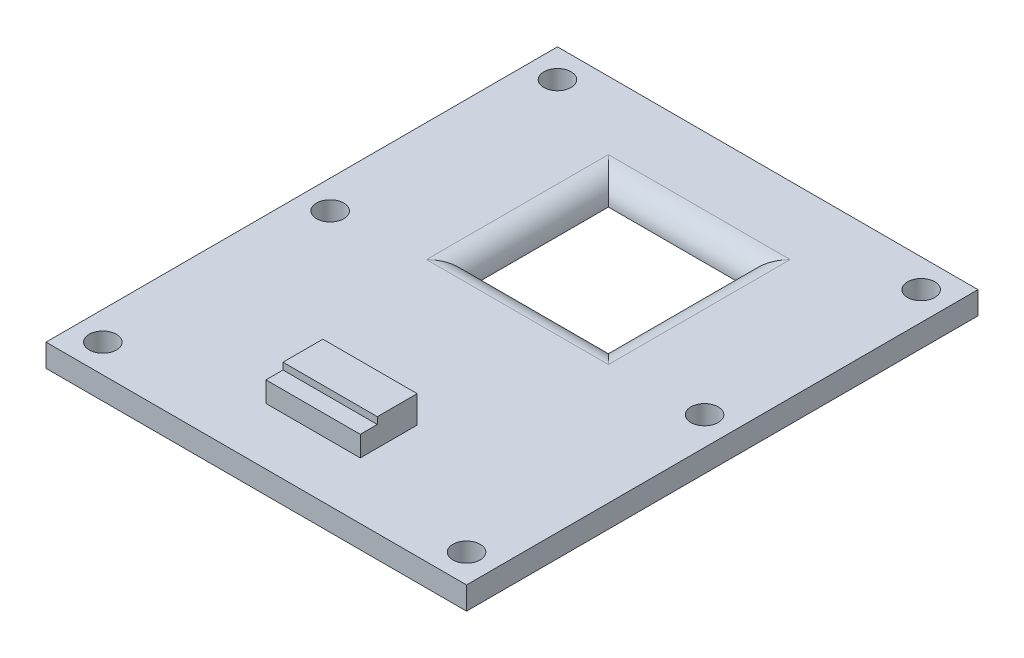
SolidWorks part; units mm, degrees
ref_plane "Front Plane" through (0, 0, 0) normal (0, 0, 1) x (1, 0, 0)
ref_plane "Top Plane" through (0, 0, 0) normal (0, 1, 0) x (1, 0, 0)
ref_plane "Right Plane" through (0, 0, 0) normal (1, 0, 0) x (0, 0, -1)
sketch "Sketch1" plane through (0, 0, 0) normal (0, 1, 0) x (1, 0, 0)
  line L1 (-10.0119, 14.0602) -> (11.9881, 14.0602)
  line L2 (-10.0119, 14.0602) -> (-10.0119, -15.9398)
  line L3 (-10.0119, -15.9398) -> (11.9881, -15.9398)
  line L4 (11.9881, 14.0602) -> (11.9881, -15.9398)
  line L5 (5.1381, -18.0598) -> (-3.1619, -18.0598)
  line L6 (5.1381, -18.0598) -> (5.1381, -13.8198)
  line L7 (5.1381, -13.8198) -> (-3.1619, -13.8198)
  line L8 (-3.1619, -18.0598) -> (-3.1619, -13.8198)
  line L9 (5.1381, -18.0598) -> (-3.1619, -13.8198) construction
  line L10 (5.1381, -13.8198) -> (-3.1619, -18.0598) construction
  line L11 (14.4881, -18.4398) -> (-12.5119, -18.4398)
  line L12 (14.4881, -18.4398) -> (14.4881, 16.5602)
  line L13 (14.4881, 16.5602) -> (-12.5119, 16.5602)
  line L14 (-12.5119, -18.4398) -> (-12.5119, 16.5602)
  line L15 (14.4881, -18.4398) -> (-12.5119, 16.5602) construction
  line L16 (14.4881, 16.5602) -> (-12.5119, -18.4398) construction
  circle A0 centre (-8.0119, 7.5602) radius 1.1746
  circle A1 centre (9.9881, 7.5602) radius 1.1992
  circle A2 centre (-8.0119, -13.9398) radius 1.1137
  circle A3 centre (9.9881, -14.2918) radius 1.0001
  point P12 (0.9881, -15.9398)
  point P17 (0.9881, -0.9398)
  dimension "D1" = 22
  dimension "D2" = 30
  dimension "D3" = 6.5
  dimension "D4" = 2
  dimension "D5" = 0
  dimension "D6" = 2
  dimension "D7" = 21.5
  dimension "D8" = 2.12
  dimension "D9" = 8.3
  dimension "D10" = 2.5
  dimension "D11" = 2.5
  dimension "D12" = 2.5
  dimension "D13" = 2.5
  dimension "D14" = 0
extrude "Boss-Extrude1" add sketch "Sketch1" along normal blind 2 contours L14 L11 L12 L13 L5 L8 L3 L2 L1 L4 L6 | L3 L8 L7 L6 L4 L1 L2 A3 A2 A1 A0 | A0 | A1 | A3 | L8 L5 L6 L3 | L8 L3 L6 L7 | A2
sketch "Sketch6" plane through (0, 2, 0) normal (0, 1, 0) x (1, 0, 0)
  line L11 (-12.5119, 16.5602) -> (14.4881, 16.5602)
  line L12 (-12.5119, 16.5602) -> (-12.5119, -18.4398)
  line L13 (-12.5119, -18.4398) -> (14.4881, -18.4398)
  line L14 (12.9881, -16.9398) -> (12.9881, 15.0602)
  line L15 (-11.0119, -16.9398) -> (12.9881, -16.9398)
  line L16 (-11.0119, 15.0602) -> (-11.0119, -16.9398)
  line L17 (12.9881, 15.0602) -> (-11.0119, 15.0602)
  line L18 (12.9881, -16.9398) -> (12.9881, 15.0602)
  line L19 (-11.0119, -16.9398) -> (12.9881, -16.9398)
  line L20 (-11.0119, 15.0602) -> (-11.0119, -16.9398)
  line L21 (12.9881, 15.0602) -> (-11.0119, 15.0602)
  line L22 (14.4881, 16.5602) -> (14.4881, -18.4398)
  dimension "D1" = 1.5
sketch "Sketch7" [suppressed] plane through (0, 0, 18.4398) normal (0, 0, 1) x (1, 0, 0)
  line L0 (-12.5119, 10.32) -> (14.4881, 10.32) construction
  line L1 (-3.2619, 10.32) -> (5.2381, 10.32)
  line L2 (-3.2619, 10.32) -> (-3.2619, 2.5)
  line L3 (-3.2619, 2.5) -> (5.2381, 2.5)
  line L4 (5.2381, 10.32) -> (5.2381, 2.5)
  line L5 (11.9881, 4) -> (7.9881, 4) construction
  dimension "D1" = 0
  dimension "D2" = 0
  dimension "D3" = 1.5
hole_wizard "M2 Clearance Hole2" [suppressed] positions "Sketch8" profile "Sketch9" hole size "M2" standard "ANSI Metric"
sketch "Sketch8" plane through (0, 2, 0) normal (0, 1, 0) x (1, 0, 0)
  point P0 (-8.0119, 7.5602)
  point P3 (9.9881, 7.5602)
  point P6 (-8.0119, -13.9398)
  point P9 (9.9881, -14.2918)
sketch "Sketch9" plane through (-8.0119, 2, -7.5602) normal (1, 0, 0) x (0, 0, 1)
  line L0 (0, 0) -> (0, 2)
  line L1 (0, 2) -> (1.2, 2)
  line L2 (1.2, 2) -> (1.2, 0)
  line L5 (1.2, 0) -> (0, 0)
  line L11 (0, -6.35) -> (0, 107.95) construction
  dimension "Thru Hole Dia." = 2.4
  dimension "Thru Hole Depth" = 2
sketch "Sketch10" plane through (0, 2, 0) normal (0, 1, 0) x (1, 0, 0)
  line L0 (11.9881, 14.0602) -> (11.9881, -15.9398) construction
  line L1 (6.9381, 1.5902) -> (-5.0619, 1.5902)
  line L2 (6.9381, 1.5902) -> (6.9381, 13.5902)
  line L3 (6.9381, 13.5902) -> (-5.0619, 13.5902)
  line L4 (-5.0619, 1.5902) -> (-5.0619, 13.5902)
  line L5 (6.9381, 1.5902) -> (-5.0619, 13.5902) construction
  line L6 (6.9381, 13.5902) -> (-5.0619, 1.5902) construction
  line L7 (-10.0119, 14.0602) -> (11.9881, 14.0602) construction
  point P0 (0.9381, 7.5902)
  dimension "D1" = 12
  dimension "D2" = 12
  dimension "D3" = 11.05
  dimension "D4" = 6.47
extrude "Cut-Extrude2" cut sketch "Sketch10" against normal up to next
fillet "Fillet1" radius 2 4 edges at (0.9381, 2, -13.5902) (6.9381, 2, -7.5902) (0.9381, 2, -1.5902) (-5.0619, 2, -7.5902)
sketch "Sketch12" plane through (0, 2, 0) normal (0, 1, 0) x (1, 0, 0)
  line L0 (-3.1619, -18.0598) -> (-3.1619, -13.8198) construction
  line L1 (-3.1619, -18.4398) -> (5.1381, -18.4398)
  line L2 (-3.1619, -18.4398) -> (-3.1619, -16.9398)
  line L3 (-3.1619, -16.9398) -> (5.1381, -16.9398)
  line L4 (5.1381, -18.4398) -> (5.1381, -16.9398)
  line L5 (5.1381, -18.0598) -> (5.1381, -13.8198) construction
  line L6 (-11.0119, -16.9398) -> (12.9881, -16.9398) construction
  line L7 (14.4881, -18.4398) -> (-12.5119, -18.4398) construction
  dimension "D1" = 0
extrude "Boss-Extrude5" add sketch "Sketch12" along normal blind 1.8
sketch "Sketch13" plane through (0, 2, 0) normal (0, 1, 0) x (1, 0, 0)
  line L0 (-3.1619, -16.9398) -> (-3.1619, -18.4398) construction
  line L1 (5.1381, -16.9398) -> (-3.1619, -16.9398)
  line L2 (5.1381, -16.9398) -> (5.1381, -13.4325)
  line L3 (5.1381, -13.4325) -> (-3.1619, -13.4325)
  line L4 (-3.1619, -16.9398) -> (-3.1619, -13.4325)
  dimension "D1" = 0
  dimension "D2" = 0
extrude "Boss-Extrude6" add sketch "Sketch13" along normal up to surface (2.3956 mm away)
sketch "Sketch14" plane through (0, 0, 0) normal (0, -1, 0) x (1, 0, 0)
  line L0 (-17.5119, -21.5602) -> (-17.5119, 23.4398) construction
  line L1 (19.4881, -21.5602) -> (-17.5119, -21.5602)
  line L2 (19.4881, -21.5602) -> (19.4881, 23.4398)
  line L3 (19.4881, 23.4398) -> (-17.5119, 23.4398)
  line L4 (-17.5119, -21.5602) -> (-17.5119, 23.4398)
  line L5 (19.4881, 23.4398) -> (9.1456, 23.4398) construction
  line L7 (14.4881, -16.5602) -> (-12.5119, -16.5602)
  line L8 (14.4881, -16.5602) -> (14.4881, 18.4398)
  line L9 (14.4881, 18.4398) -> (-12.5119, 18.4398)
  line L10 (-12.5119, -16.5602) -> (-12.5119, 18.4398)
extrude "Boss-Extrude7" add sketch "Sketch14" against normal up to surface (2 mm away) up to face at (0.9381, 2, -7.5902)
hole_wizard "M2 Clearance Hole3" positions "Sketch15" profile "Sketch16" hole size "M2" standard "ANSI Metric" end condition through all
sketch "Sketch15" plane through (0, 0, 0) normal (0, -1, 0) x (-1, 0, 0)
  point P0 (-16.9881, 19.0602)
  point P3 (15.0119, 19.0602)
  point P6 (15.0119, -0.9398)
  point P9 (15.0119, -20.9398)
  point P12 (-16.9881, -20.9398)
  point P15 (-16.9881, 0)
sketch "Sketch16" plane through (16.9881, 0, -19.0602) normal (1, 0, 0) x (0, 0, -1)
  line L0 (0, 0) -> (0, 4.3956)
  line L1 (0, 4.3956) -> (1.2, 4.3956)
  line L2 (1.2, 4.3956) -> (1.2, 0)
  line L5 (1.2, 0) -> (0, 0)
  line L11 (0, -6.35) -> (0, 107.95) construction
  dimension "Thru Hole Dia." = 2.4
  dimension "Thru Hole Depth" = 4.3956
